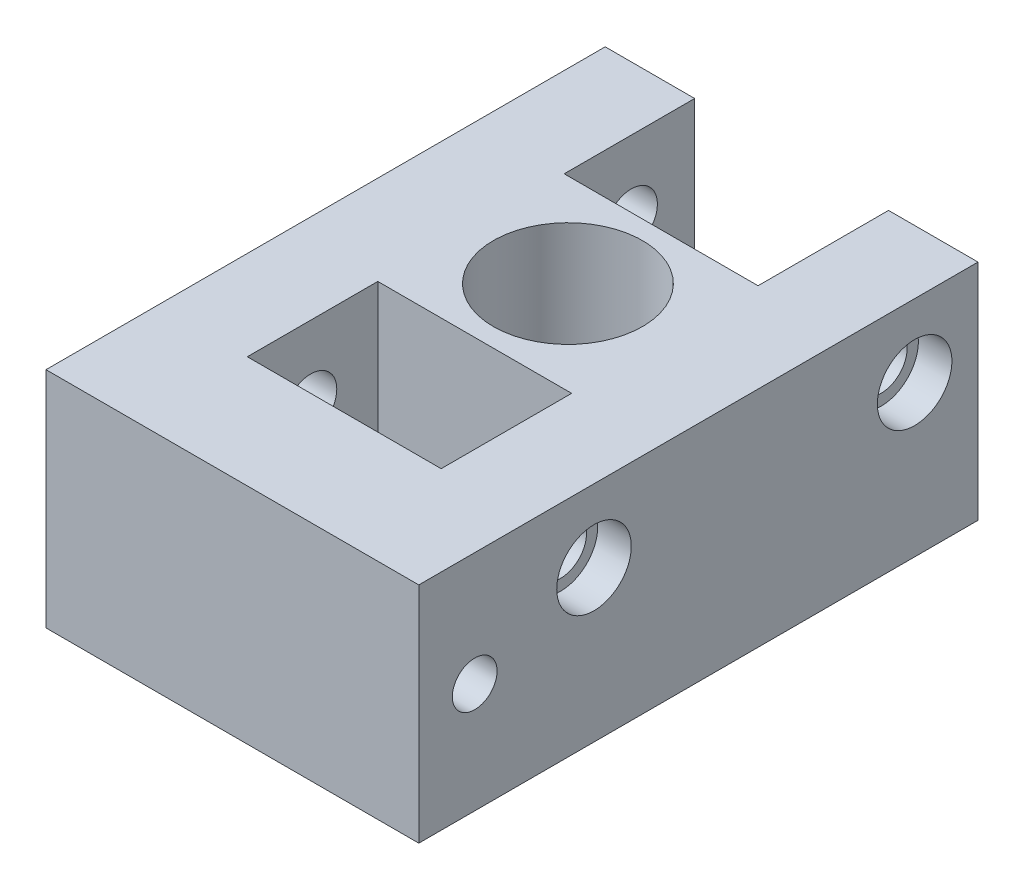
SolidWorks part; units mm, degrees
ref_plane "前视基准面" through (0, 0, 0) normal (0, 0, 1) x (1, 0, 0)
ref_plane "上视基准面" through (0, 0, 0) normal (0, 1, 0) x (1, 0, 0)
ref_plane "右视基准面" through (0, 0, 0) normal (1, 0, 0) x (0, 0, -1)
other "Configuration Table"
sketch "草图1" plane through (0, 0, 0) normal (0, 1, 0) x (1, 0, 0)
  line L1 (0, 0) -> (10, 0)
  line L2 (0, 0) -> (0, -12)
  line L3 (0, -12) -> (10, -12)
  line L4 (10, 0) -> (10, -12)
  dimension "D4" = 10
  dimension "D11" = 12
extrude "凸台-拉伸1" add sketch "草图1" along normal blind 6
sketch "草图2" plane through (0, 6, 0) normal (0, 1, 0) x (1, 0, 0)
  circle A0 centre (5, -1.5) radius 2
  circle A1 centre (5, -10.5) radius 2
  circle A2 centre (5, -1.5) radius 1
  circle A3 centre (5, -10.5) radius 1
  dimension "D1" = 2
  dimension "D2" = 4
extrude "切除-拉伸1" cut sketch "草图2" against normal through all contours A2 | A3
extrude "切除-拉伸2" cut sketch "草图2<3>" against normal offset from surface (4 mm away) 2 contours A0 | A1 up to face at (5, 0, 2.5)
sketch "草图2<3>" plane through (0, 6, 0) normal (0, 1, 0) x (1, 0, 0) same geometry as "草图2"
sketch "草图3" plane through (0, 6, 0) normal (0, 1, 0) x (1, 0, 0)
  line L0 (10, 0) -> (0, -12)
  circle A0 centre (5, -6) radius 2
  dimension "D1" = 4
extrude "切除-拉伸3" cut sketch "草图3" against normal through all contours A0
sketch "草图4" plane through (0, 6, 0) normal (0, 1, 0) x (1, 0, 0)
  line L0 (10, 0) -> (6.3229, 0) construction
  line L1 (7.6, 0) -> (2.4, 0)
  line L2 (7.6, 0) -> (7.6, -3.5)
  line L3 (7.6, -3.5) -> (2.4, -3.5)
  line L4 (2.4, 0) -> (2.4, -3.5)
  line L5 (6.3229, -12) -> (10, -12) construction
  line L6 (7.6, -12) -> (2.4, -12)
  line L7 (7.6, -12) -> (7.6, -8.5)
  line L8 (7.6, -8.5) -> (2.4, -8.5)
  line L9 (2.4, -12) -> (2.4, -8.5)
  line L10 (10, -12) -> (10, 0) construction
  line L11 (0, 0) -> (0, -12) construction
  arc A0 (3.6771, 0) -> (6.3229, 0) centre (5, -1.5) ccw construction
  arc A1 (6.3229, -12) -> (3.6771, -12) centre (5, -10.5) ccw construction
  dimension "D1" = 2.4
  dimension "D2" = 2.4
extrude "切除-拉伸4" cut sketch "草图4" against normal up to surface (4 mm away) contours L4 L3 L2 L1 | L9 L8 L7 L6 up to face at (5, 2, 2.5)
sketch "草图6" plane through (0, 0, 0) normal (-1, 0, 0) x (0, 0, 1)
  circle A0 centre (1.7, 4.05) radius 1
  circle A1 centre (10.3, 4.05) radius 1
  circle A2 centre (1.7, 4.05) radius 0.7
  circle A3 centre (10.3, 4.05) radius 0.7
  dimension "D1" = 2
  dimension "D2" = 1.4
extrude "切除-拉伸5" cut sketch "草图6" against normal through all contours A2 | A3
extrude "切除-拉伸6" cut sketch "草图6<3>" against normal offset from surface (0.9 mm away) 1.5 contours A0 | A1 up to face at (2.4, 4.05, 2.4)
sketch "草图6<3>" plane through (0, 0, 0) normal (-1, 0, 0) x (0, 0, 1) same geometry as "草图6"
extrude "切除-拉伸7" cut sketch "草图6<4>" along normal offset from surface (0.9 mm away) 1.5 from surface contours A0 | A1 up to face at (7.6, 4.05, 2.4) starting at face at (10, 4.05, 2.4)
sketch "草图6<4>" plane through (0, 0, 0) normal (-1, 0, 0) x (0, 0, 1) same geometry as "草图6"
sketch "草图7" plane through (0, 0, 12) normal (0, 0, 1) x (1, 0, 0)
  line L0 (0, 0) -> (10, 0) construction
  line L1 (0, 0) -> (10, 0)
  line L2 (0, 0) -> (0, 6)
  line L3 (0, 6) -> (10, 6)
  line L4 (10, 0) -> (10, 6)
  point P4 (5, 0)
  dimension "D1" = 6
  dimension "D2" = 10
extrude "凸台-拉伸3" add sketch "草图7" along normal blind 3 contours L1 L4 L3 L2
sketch "草图8" plane through (10, 0, 0) normal (1, 0, 0) x (0, 0, -1)
  line L0 (-15, 0) -> (-15, 6) construction
  circle A0 centre (-13.5, 2.9514) radius 0.6
  dimension "D2" = 1.2
  dimension "D1" = 1.5
extrude "切除-拉伸8" cut sketch "草图8" against normal through all contours A0
